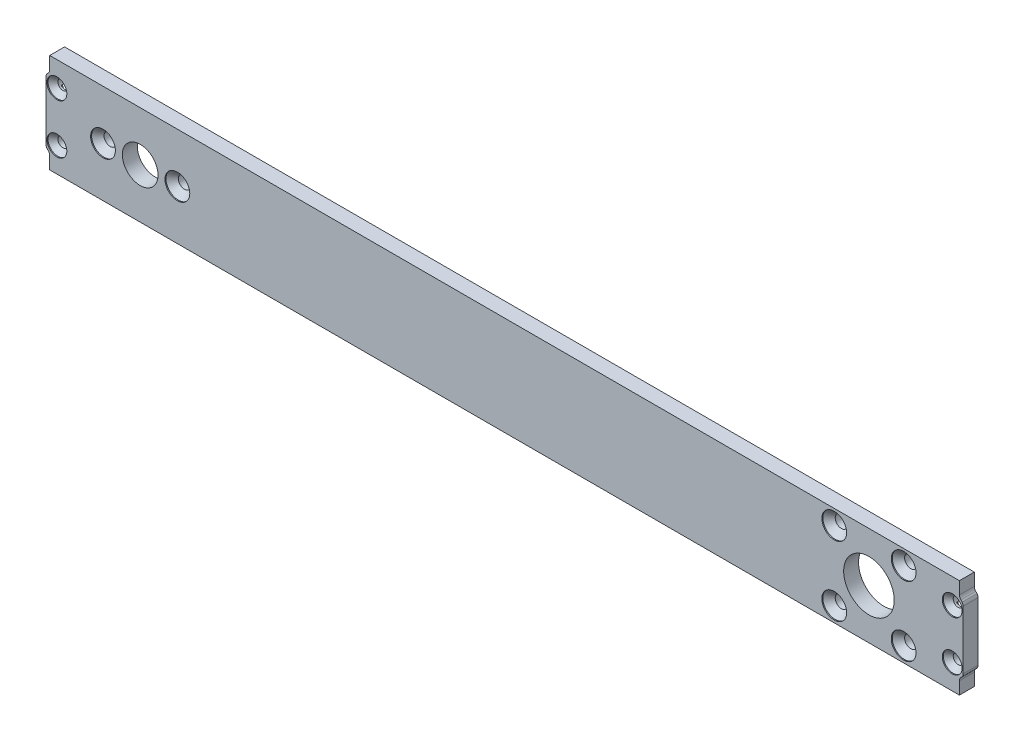
SolidWorks part; units mm, degrees
ref_plane "Front Plane" through (0, 0, 0) normal (0, 0, 1) x (1, 0, 0)
ref_plane "Top Plane" through (0, 0, 0) normal (0, 1, 0) x (1, 0, 0)
ref_plane "Right Plane" through (0, 0, 0) normal (1, 0, 0) x (0, 0, -1)
sketch "Sketch1" plane through (0, 0, 0) normal (0, 0, 1) x (1, 0, 0)
  line L1 (-92.5, 10) -> (92.5, 10)
  line L2 (-92.5, 10) -> (-92.5, -10)
  line L3 (-92.5, -10) -> (92.5, -10)
  line L4 (92.5, 10) -> (92.5, -10)
  line L5 (-92.5, 10) -> (92.5, -10) construction
  line L6 (-92.5, -10) -> (92.5, 10) construction
  point P0 (0, 0)
  dimension "D1" = 20
  dimension "D2" = 185
extrude "Base shape" add sketch "Sketch1" against normal blind 3
sketch "Sketch2" plane through (0, 0, 0) normal (0, 0, 1) x (1, 0, 0)
  line L0 (-83.5, 10) -> (-83.5, -10) construction
  line L1 (92.5, 10) -> (-92.5, 10) construction
  line L2 (-92.5, -10) -> (92.5, -10) construction
  line L3 (-92.5, 10) -> (-92.5, -10) construction
  line L4 (-92.5, 0) -> (92.5, 0) construction
  line L5 (92.5, -10) -> (92.5, 10) construction
  line L6 (-73.5, 10) -> (-73.5, -10) construction
  line L7 (0, 10) -> (0, -10) construction
  line L8 (73.5, 5.1) -> (92.5, 5.1) construction
  line L9 (-73.5, 3.6) -> (-92.5, 3.6) construction
  line L11 (80.5, -7) -> (66.5, -7)
  line L12 (80.5, -7) -> (80.5, 7)
  line L13 (80.5, 7) -> (66.5, 7)
  line L14 (66.5, -7) -> (66.5, 7)
  line L15 (80.5, -7) -> (66.5, 7) construction
  line L16 (80.5, 7) -> (66.5, -7) construction
  circle A0 centre (-73.5, 0) radius 10
  circle A1 centre (-81, 0) radius 1.25
  circle A2 centre (-66, 0) radius 1.25
  circle A3 centre (-73.5, 0) radius 3.6
  circle A4 centre (73.5, 0) radius 5.1
  circle A5 centre (66.5, 7) radius 1.25
  circle A6 centre (80.5, 7) radius 1.25
  circle A7 centre (80.5, -7) radius 1.25
  circle A8 centre (66.5, -7) radius 1.25
  dimension "D2" = 20
  dimension "D3" = 2.5
  dimension "D4" = 15
  dimension "D5" = 7.2
  dimension "D6" = 10.2
  dimension "D8" = 2.5
  dimension "D1" = 147
  dimension "D7" = 14
extrude "Motor cutouts" cut sketch "Sketch2" against normal up to next contours A5 | A6 | A7 | A8 | A1 | A2 | A3 | A4
sketch "Sketch5" plane through (0, 0, -3) normal (0, 0, -1) x (-1, 0, 0)
  line L0 (0, 10) -> (0, -10) construction
  line L3 (-92.5, 10) -> (92.5, 10) construction
  line L4 (92.5, -10) -> (-92.5, -10) construction
  line L5 (-60, -7) -> (60, -7) construction
  line L6 (-60, -6) -> (60, -6)
  line L7 (-60, -8) -> (60, -8)
  arc A0 (-60, -6) -> (-60, -8) centre (-60, -7) ccw
  arc A1 (60, -8) -> (60, -6) centre (60, -7) ccw
  point P8 (0, -7)
  dimension "D1" = 120
  dimension "D2" = 2
  dimension "D3" = 2
extrude "PCB slot" cut sketch "Sketch5" against normal blind 0.775
sketch "Sketch6" plane through (0, 0, 0) normal (0, 0, 1) x (1, 0, 0)
  line L0 (90.3, 10) -> (90.3, -10) construction
  line L1 (92.5, 10) -> (-92.5, 10) construction
  line L2 (-92.5, -10) -> (92.5, -10) construction
  line L3 (92.5, -10) -> (92.5, 10) construction
  line L4 (92.5, 0) -> (-92.5, 0) construction
  line L5 (-92.5, 10) -> (-92.5, -10) construction
  line L6 (0, 10) -> (0, -10) construction
  circle A0 centre (90.3, 5) radius 1
  circle A2 centre (90.3, -5) radius 1
  circle A3 centre (-90.3, -5) radius 1
  circle A5 centre (-90.3, 5) radius 1
  dimension "D2" = 2
  dimension "D1" = 2.2
  dimension "D3" = 10
extrude "End plate holes" cut sketch "Sketch6" against normal up to next
hole_wizard "Motor M2.5 countersunks" positions "Sketch3" profile "Sketch4" countersink size "M2.5" standard "ANSI Metric" end condition through all
sketch "Sketch3" plane through (0, 0, 0) normal (0, 0, 1) x (1, 0, 0)
  point P0 (-81, 0)
  point P3 (-66, 0)
  point P7 (66.5, 7)
  point P10 (80.5, 7)
  point P13 (66.5, -7)
  point P16 (80.5, -7)
sketch "Sketch4" plane through (-81, 0, 0) normal (1, 0, 0) x (0, -1, 0)
  line L0 (0, 0) -> (0, 3)
  line L1 (0, 3) -> (1.25, 3)
  line L2 (1.25, 3) -> (1.25, 1.45)
  line L3 (1.25, 1.45) -> (2.5, 0.2)
  line L4 (2.5, 0.2) -> (2.5, 0)
  line L6 (2.5, 0) -> (0, 0)
  line L7 (-1.25, 1.45) -> (-2.5, 0.2) construction
  line L11 (0, -6.35) -> (0, 107.95) construction
  dimension "Thru Hole Dia." = 2.5
  dimension "Thru Hole Depth" = 3
  dimension "C'Sink Dia." = 5
  dimension "C'Sink Angle" = 90
  dimension "Head Clearance" = 0.2
hole_wizard "End M2 countersunks" positions "Sketch10" profile "Sketch9" countersink size "M2" standard "ANSI Metric" end condition through all
sketch "Sketch10" plane through (0, 0, 0) normal (0, 0, 1) x (1, 0, 0)
  point P2 (90.3, 5)
  point P8 (90.3, -5)
  point P11 (-90.3, 5)
  point P17 (-90.3, -5)
sketch "Sketch9" plane through (90.3, 5, 0) normal (1, 0, 0) x (0, -1, 0)
  line L0 (0, 0) -> (0, 3)
  line L1 (0, 3) -> (1, 3)
  line L2 (1, 3) -> (1, 1.2)
  line L3 (1, 1.2) -> (2, 0.2)
  line L4 (2, 0.2) -> (2, 0)
  line L6 (2, 0) -> (0, 0)
  line L7 (-1, 1.2) -> (-2, 0.2) construction
  line L11 (0, -6.35) -> (0, 107.95) construction
  dimension "Thru Hole Dia." = 2
  dimension "Thru Hole Depth" = 3
  dimension "C'Sink Dia." = 4
  dimension "C'Sink Angle" = 90
  dimension "Head Clearance" = 0.2
sketch "Sketch12" plane through (0, 0, -3) normal (0, 0, -1) x (-1, 0, 0)
  line L0 (-92.5, 0) -> (92.5, 0) construction
  line L1 (-92.5, -10) -> (-92.5, 10) construction
  line L2 (92.5, 10) -> (92.5, -10) construction
  line L3 (-90.3, 5) -> (-90.3, -5) construction
  line L4 (-88.7, 4.05) -> (-91.9, 0.85) construction
  line L5 (-91.9, 4.05) -> (-88.7, 4.05)
  line L6 (-91.9, 4.05) -> (-91.9, -4.05)
  line L7 (-91.9, -4.05) -> (-88.7, -4.05)
  line L8 (-88.7, 4.05) -> (-88.7, -4.05)
  line L9 (-91.9, 4.05) -> (-88.7, -4.05) construction
  line L10 (-91.9, -4.05) -> (-88.7, 4.05) construction
  line L11 (0, 10) -> (0, -10) construction
  line L12 (-92.5, 10) -> (92.5, 10) construction
  line L13 (92.5, -10) -> (-92.5, -10) construction
  line L14 (91.9, -4.05) -> (88.7, -4.05)
  line L15 (91.9, 4.05) -> (88.7, 4.05)
  line L16 (91.9, 4.05) -> (91.9, -4.05)
  line L17 (88.7, 4.05) -> (88.7, -4.05)
  line L18 (-91.1929, 4.3429) -> (-89.4071, 4.3429)
  line L19 (-91.1929, -4.3429) -> (-89.4071, -4.3429)
  line L20 (91.1929, 4.3429) -> (89.4071, 4.3429)
  line L21 (91.1929, -4.3429) -> (89.4071, -4.3429)
  circle A0 centre (-89.4071, 3.3429) radius 1
  circle A1 centre (-91.1929, 3.3429) radius 1
  circle A2 centre (-89.4071, -3.3429) radius 1
  circle A3 centre (-91.1929, -3.3429) radius 1
  circle A4 centre (89.4071, -3.3429) radius 1
  circle A5 centre (91.1929, -3.3429) radius 1
  circle A6 centre (89.4071, 3.3429) radius 1
  circle A7 centre (91.1929, 3.3429) radius 1
  point P10 (-90.3, 0)
  circle M9 centre (-90.3, -5) radius 1
  circle M10 centre (90.3, -5) radius 1
  circle M11 centre (90.3, 5) radius 1
  circle M12 centre (-90.3, 5) radius 1
  dimension "D3" = 2
  dimension "D1" = 3.2
  dimension "D2" = 8.1
  dimension "D4" = 45
extrude "Tap slots" cut sketch "Sketch12" against normal blind 1.4 contours A1 L5 A0 L18 M12 | A3 L19 A2 L7 M9 | A7 L20 A6 L15 M11 | A5 L14 A4 L21 M10 | A1 | A0 | A2 | A3 | L6 L7 L8 L5 | A6 | A7 | A5 | A4 | L17 L14 L16 L15 region at (90.3, 4.2292, -3) region at (90.3, -4.2292, -3) region at (-90.3, -4.2292, -3) region at (-90.3, 4.2292, -3)
sketch "Sketch13" plane through (0, 0, 0) normal (0, 0, 1) x (1, 0, 0)
  line L0 (-92.5, -10) -> (92.5, -10) construction
  line L1 (-92.5, 10) -> (-91.75, 10)
  line L2 (-92.5, 10) -> (-92.5, -10)
  line L3 (-92.5, -10) -> (-91.75, -10)
  line L4 (-91.75, 10) -> (-91.75, -10)
  line L5 (-92.5, 0) -> (92.5, 0) construction
  line L6 (92.5, -10) -> (92.5, 10) construction
  line L7 (0, 10) -> (0, -10) construction
  line L8 (92.5, 10) -> (-92.5, 10) construction
  line L9 (92.5, -10) -> (91.75, -10)
  line L10 (91.75, 10) -> (91.75, -10)
  line L11 (92.5, 10) -> (91.75, 10)
  line L12 (92.5, 10) -> (92.5, -10)
  circle A0 centre (-90.3, 5) radius 2.5
  circle A1 centre (-90.3, -5) radius 2.5
  circle A2 centre (90.3, 5) radius 2.5
  circle A3 centre (90.3, -5) radius 2.5
  line M16 (92.5, -10) -> (92.5, 10)
  line M17 (92.5, 10) -> (-92.5, 10)
  line M18 (-92.5, 10) -> (-92.5, -10)
  line M19 (-92.5, -10) -> (92.5, -10)
  dimension "D2" = 5
  dimension "D1" = 0.75
extrude "Cut-Extrude3" cut sketch "Sketch13" against normal up to next contours A0 L4 M17 M18 | A1 L4 M18 M19 | L10 A2 M16 M17 | A3 L10 M16 M19 region at (-92.1406, 8.3301, 0) region at (92.1406, 8.3301, 0) region at (-92.1406, -8.3301, 0) region at (92.1406, -8.3301, 0)
fillet "Fillet1" radius 1 8 edges at (-91.75, -7.0365, -1.5) (-92.5, -6.1874, -1.5) (-92.5, 6.1874, -1.5) (-91.75, 7.0365, -1.5) (92.5, 6.1874, -1.5) (91.75, 7.0365, -1.5) (92.5, -6.1874, -1.5) (91.75, -7.0365, -1.5)
